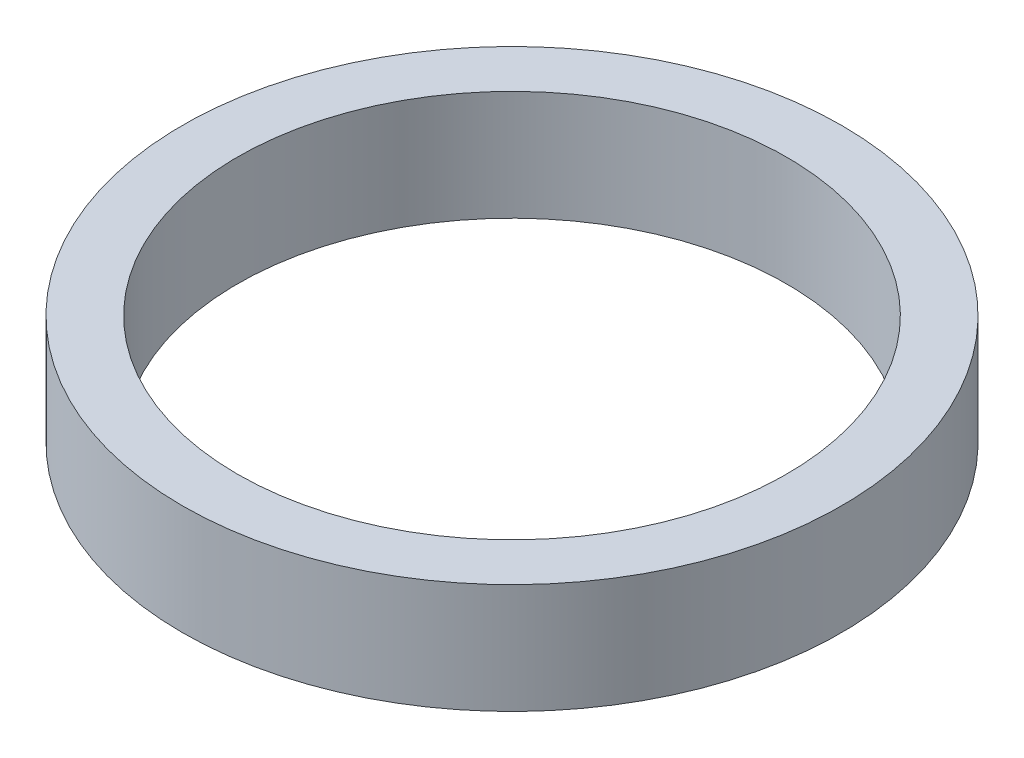
SolidWorks part; units mm, degrees
ref_plane "Front Plane" through (0, 0, 0) normal (0, 0, 1) x (1, 0, 0)
ref_plane "Top Plane" through (0, 0, 0) normal (0, 1, 0) x (1, 0, 0)
ref_plane "Right Plane" through (0, 0, 0) normal (1, 0, 0) x (0, 0, -1)
sketch "Sketch1" plane through (0, 0, 0) normal (0, 1, 0) x (1, 0, 0)
  circle A0 centre (0, 0) radius 60
  dimension "FLANGE_OD" = 120
extrude "Boss-Extrude1" add sketch "Sketch1" along normal blind 20
sketch "Sketch2" plane through (0, 0, 0) normal (0, 1, 0) x (1, 0, 0)
  circle A0 centre (0, 0) radius 50
  dimension "BORE_D" = 100
extrude "Cut-Extrude1" cut sketch "Sketch2" along normal through all
sketch "Sketch3" plane through (0, 20, 0) normal (0, 1, 0) x (1, 0, 0)
  circle A0 centre (0, 0) radius 26.7441 construction
  circle A1 centre (-26.7441, 0) radius 1.521
  dimension "BOLT_D" = 3.0421
  dimension "BOLT_PCD" = 53.4882
extrude "Cut-Extrude2" cut sketch "Sketch3" against normal blind 14.5675 rebuild error yes
pattern_circular "CirPattern1" count 4 over 360 rebuild error yes
